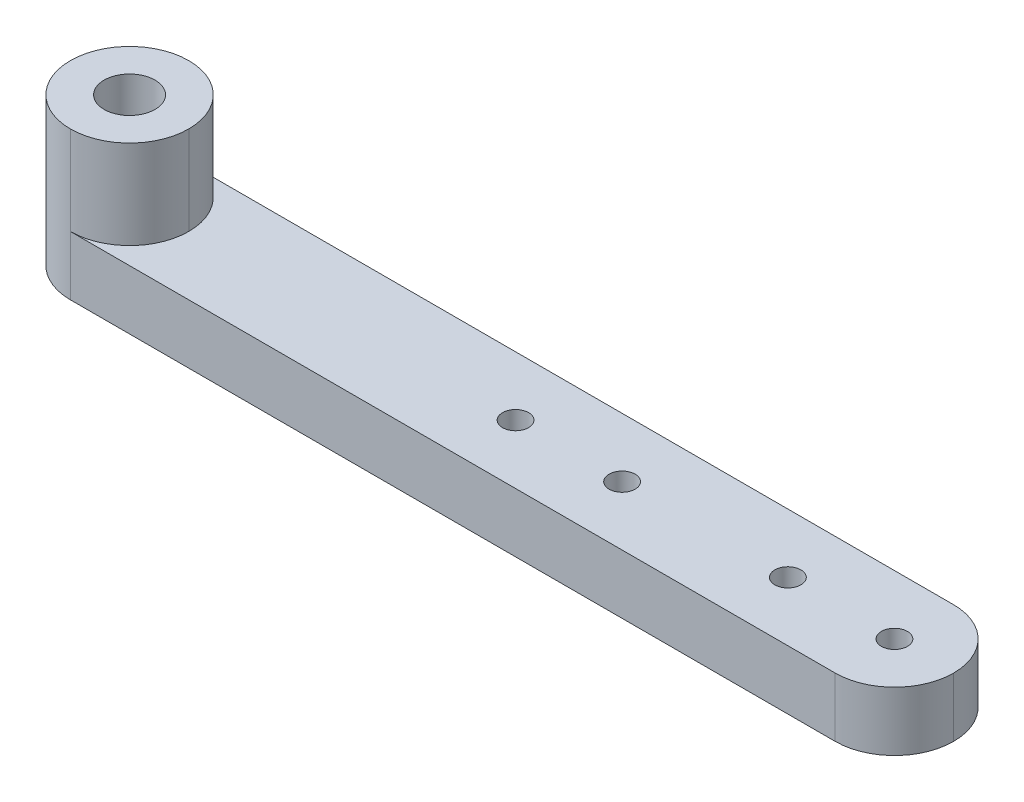
SolidWorks part; units mm, degrees
ref_plane "정면" through (0, 0, 0) normal (0, 0, 1) x (1, 0, 0)
ref_plane "윗면" through (0, 0, 0) normal (0, 1, 0) x (1, 0, 0)
ref_plane "우측면" through (0, 0, 0) normal (1, 0, 0) x (0, 0, -1)
sketch "스케치1" plane through (0, 0, 0) normal (0, 0, 1) x (1, 0, 0)
  line L1 (-37.3, -2.5) -> (37.3, -2.5)
  line L2 (-37.3, -2.5) -> (-37.3, 2.5)
  line L3 (-37.3, 2.5) -> (37.3, 2.5)
  line L4 (37.3, -2.5) -> (37.3, 2.5)
  line L5 (-37.3, -2.5) -> (37.3, 2.5) construction
  line L6 (-37.3, 2.5) -> (37.3, -2.5) construction
  point P0 (0, 0)
  dimension "D1" = 74.6
  dimension "D2" = 5
extrude "보스-돌출1" add sketch "스케치1" along normal blind 10
sketch "스케치4" plane through (0, 2.5, 0) normal (0, 1, 0) x (1, 0, 0)
  line L0 (37.3, 0) -> (-37.3, 0) construction
  line L1 (-27.3, 0) -> (-37.3, 0)
  line L2 (-27.3, 0) -> (-27.3, -10)
  line L3 (-27.3, -10) -> (-37.3, -10)
  line L4 (-37.3, 0) -> (-37.3, -10)
  line L5 (-37.3, -10) -> (-37.3, 0) construction
  dimension "D1" = 10
extrude "보스-돌출2" add sketch "스케치4" along normal blind 7.5
fillet "필렛1" radius 5 6 edges at (37.3, 0, 10) (37.3, 0, 0) (-37.3, 3.75, 0) (-37.3, 3.75, 10) (-27.3, 6.25, 10) (-27.3, 6.25, 0)
sketch "스케치2" plane through (0, 10, 0) normal (0, 1, 0) x (1, 0, 0)
  line L0 (23.3, -5) -> (32.3, -5) construction
  line L1 (0.3, -5) -> (9.3, -5) construction
  circle A0 centre (-32.3, -5) radius 2.15
  circle A1 centre (32.3, -5) radius 1.1
  circle A3 centre (23.3, -5) radius 1.1
  circle A5 centre (9.3, -5) radius 1.1
  circle A7 centre (0.3, -5) radius 1.1
  dimension "D1" = 4.3
  dimension "D2" = 2.2
  dimension "D3" = 9
  dimension "D4" = 9
  dimension "D9" = 2.2
  dimension "D10" = 14
extrude "컷-돌출1" cut sketch "스케치2" against normal through all
